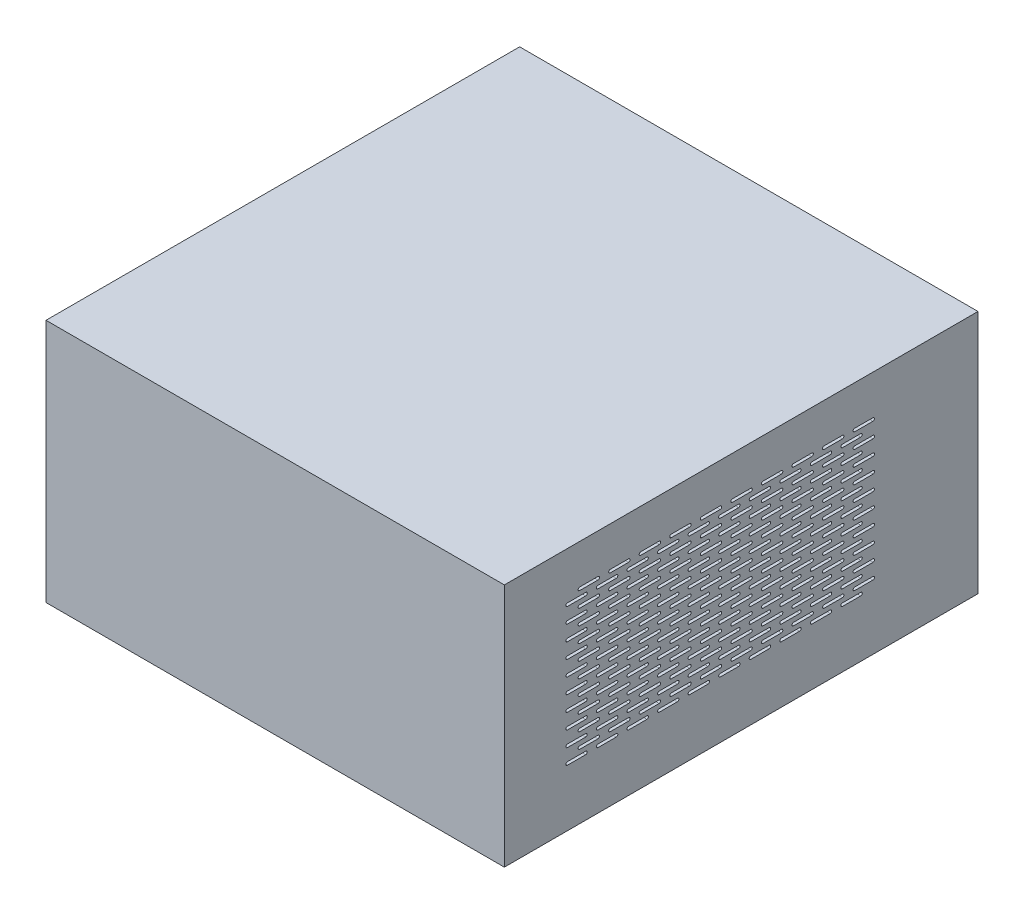
SolidWorks part; units mm, degrees
ref_plane "前视基准面" through (0, 0, 0) normal (0, 0, 1) x (1, 0, 0)
ref_plane "上视基准面" through (0, 0, 0) normal (0, 1, 0) x (1, 0, 0)
ref_plane "右视基准面" through (0, 0, 0) normal (1, 0, 0) x (0, 0, -1)
sketch "草图1" plane through (0, 0, 0) normal (0, 0, 1) x (1, 0, 0)
  line L1 (-75, 40) -> (75, 40)
  line L2 (-75, 40) -> (-75, -40)
  line L3 (-75, -40) -> (75, -40)
  line L4 (75, 40) -> (75, -40)
  line L5 (-75, 40) -> (75, -40) construction
  line L6 (-75, -40) -> (75, 40) construction
  point P0 (0, 0)
  dimension "D1" = 150
  dimension "D2" = 80
extrude "凸台-拉伸1" add sketch "草图1" along normal blind 77.5 and the other way blind 77.5 contours L1 L4 L3 L2
shell "抽壳1" thickness 2.3 removed face at (0, 0, -77.5)
sketch "草图2" plane through (75, 0, 0) normal (1, 0, 0) x (0, 0, -1)
  line L0 (-46.8721, 27.0767) -> (-52.8721, 27.0767)
  line L1 (-46.8721, 26.0767) -> (-52.8721, 26.0767)
  line L2 (-36.8721, 27.0767) -> (-42.8721, 27.0767)
  line L3 (-36.8721, 26.0767) -> (-42.8721, 26.0767)
  line L4 (-26.8721, 27.0767) -> (-32.8721, 27.0767)
  line L5 (-26.8721, 26.0767) -> (-32.8721, 26.0767)
  line L6 (-16.8721, 27.0767) -> (-22.8721, 27.0767)
  line L7 (-16.8721, 26.0767) -> (-22.8721, 26.0767)
  line L8 (-6.8721, 27.0767) -> (-12.8721, 27.0767)
  line L9 (-6.8721, 26.0767) -> (-12.8721, 26.0767)
  line L10 (3.1279, 27.0767) -> (-2.8721, 27.0767)
  line L11 (3.1279, 26.0767) -> (-2.8721, 26.0767)
  line L12 (13.1279, 27.0767) -> (7.1279, 27.0767)
  line L13 (13.1279, 26.0767) -> (7.1279, 26.0767)
  line L14 (23.1279, 27.0767) -> (17.1279, 27.0767)
  line L15 (23.1279, 26.0767) -> (17.1279, 26.0767)
  line L16 (33.1279, 27.0767) -> (27.1279, 27.0767)
  line L17 (33.1279, 26.0767) -> (27.1279, 26.0767)
  line L18 (43.1279, 27.0767) -> (37.1279, 27.0767)
  line L19 (43.1279, 26.0767) -> (37.1279, 26.0767)
  line L20 (-50.8721, 24.5767) -> (-56.8721, 24.5767)
  line L21 (-50.8721, 23.5767) -> (-56.8721, 23.5767)
  line L22 (-40.8721, 24.5767) -> (-46.8721, 24.5767)
  line L23 (-40.8721, 23.5767) -> (-46.8721, 23.5767)
  line L24 (-30.8721, 24.5767) -> (-36.8721, 24.5767)
  line L25 (-30.8721, 23.5767) -> (-36.8721, 23.5767)
  line L26 (-20.8721, 24.5767) -> (-26.8721, 24.5767)
  line L27 (-20.8721, 23.5767) -> (-26.8721, 23.5767)
  line L28 (-10.8721, 24.5767) -> (-16.8721, 24.5767)
  line L29 (-10.8721, 23.5767) -> (-16.8721, 23.5767)
  line L30 (-0.8721, 24.5767) -> (-6.8721, 24.5767)
  line L31 (-0.8721, 23.5767) -> (-6.8721, 23.5767)
  line L32 (9.1279, 24.5767) -> (3.1279, 24.5767)
  line L33 (9.1279, 23.5767) -> (3.1279, 23.5767)
  line L34 (19.1279, 24.5767) -> (13.1279, 24.5767)
  line L35 (19.1279, 23.5767) -> (13.1279, 23.5767)
  line L36 (29.1279, 24.5767) -> (23.1279, 24.5767)
  line L37 (29.1279, 23.5767) -> (23.1279, 23.5767)
  line L38 (39.1279, 24.5767) -> (33.1279, 24.5767)
  line L39 (39.1279, 23.5767) -> (33.1279, 23.5767)
  line L40 (-46.8721, 22.0767) -> (-52.8721, 22.0767)
  line L41 (-46.8721, 21.0767) -> (-52.8721, 21.0767)
  line L42 (-36.8721, 22.0767) -> (-42.8721, 22.0767)
  line L43 (-36.8721, 21.0767) -> (-42.8721, 21.0767)
  line L44 (-26.8721, 22.0767) -> (-32.8721, 22.0767)
  line L45 (-26.8721, 21.0767) -> (-32.8721, 21.0767)
  line L46 (-16.8721, 22.0767) -> (-22.8721, 22.0767)
  line L47 (-16.8721, 21.0767) -> (-22.8721, 21.0767)
  line L48 (-6.8721, 22.0767) -> (-12.8721, 22.0767)
  line L49 (-6.8721, 21.0767) -> (-12.8721, 21.0767)
  line L50 (3.1279, 22.0767) -> (-2.8721, 22.0767)
  line L51 (3.1279, 21.0767) -> (-2.8721, 21.0767)
  line L52 (13.1279, 22.0767) -> (7.1279, 22.0767)
  line L53 (13.1279, 21.0767) -> (7.1279, 21.0767)
  line L54 (23.1279, 22.0767) -> (17.1279, 22.0767)
  line L55 (23.1279, 21.0767) -> (17.1279, 21.0767)
  line L56 (33.1279, 22.0767) -> (27.1279, 22.0767)
  line L57 (33.1279, 21.0767) -> (27.1279, 21.0767)
  line L58 (43.1279, 22.0767) -> (37.1279, 22.0767)
  line L59 (43.1279, 21.0767) -> (37.1279, 21.0767)
  line L60 (-50.8721, 19.5767) -> (-56.8721, 19.5767)
  line L61 (-50.8721, 18.5767) -> (-56.8721, 18.5767)
  line L62 (-40.8721, 19.5767) -> (-46.8721, 19.5767)
  line L63 (-40.8721, 18.5767) -> (-46.8721, 18.5767)
  line L64 (-30.8721, 19.5767) -> (-36.8721, 19.5767)
  line L65 (-30.8721, 18.5767) -> (-36.8721, 18.5767)
  line L66 (-20.8721, 19.5767) -> (-26.8721, 19.5767)
  line L67 (-20.8721, 18.5767) -> (-26.8721, 18.5767)
  line L68 (-10.8721, 19.5767) -> (-16.8721, 19.5767)
  line L69 (-10.8721, 18.5767) -> (-16.8721, 18.5767)
  line L70 (-0.8721, 19.5767) -> (-6.8721, 19.5767)
  line L71 (-0.8721, 18.5767) -> (-6.8721, 18.5767)
  line L72 (9.1279, 19.5767) -> (3.1279, 19.5767)
  line L73 (9.1279, 18.5767) -> (3.1279, 18.5767)
  line L74 (19.1279, 19.5767) -> (13.1279, 19.5767)
  line L75 (19.1279, 18.5767) -> (13.1279, 18.5767)
  line L76 (29.1279, 19.5767) -> (23.1279, 19.5767)
  line L77 (29.1279, 18.5767) -> (23.1279, 18.5767)
  line L78 (39.1279, 19.5767) -> (33.1279, 19.5767)
  line L79 (39.1279, 18.5767) -> (33.1279, 18.5767)
  line L80 (-46.8721, 17.0767) -> (-52.8721, 17.0767)
  line L81 (-46.8721, 16.0767) -> (-52.8721, 16.0767)
  line L82 (-36.8721, 17.0767) -> (-42.8721, 17.0767)
  line L83 (-36.8721, 16.0767) -> (-42.8721, 16.0767)
  line L84 (-26.8721, 17.0767) -> (-32.8721, 17.0767)
  line L85 (-26.8721, 16.0767) -> (-32.8721, 16.0767)
  line L86 (-16.8721, 17.0767) -> (-22.8721, 17.0767)
  line L87 (-16.8721, 16.0767) -> (-22.8721, 16.0767)
  line L88 (-6.8721, 17.0767) -> (-12.8721, 17.0767)
  line L89 (-6.8721, 16.0767) -> (-12.8721, 16.0767)
  line L90 (3.1279, 17.0767) -> (-2.8721, 17.0767)
  line L91 (3.1279, 16.0767) -> (-2.8721, 16.0767)
  line L92 (13.1279, 17.0767) -> (7.1279, 17.0767)
  line L93 (13.1279, 16.0767) -> (7.1279, 16.0767)
  line L94 (23.1279, 17.0767) -> (17.1279, 17.0767)
  line L95 (23.1279, 16.0767) -> (17.1279, 16.0767)
  line L96 (33.1279, 17.0767) -> (27.1279, 17.0767)
  line L97 (33.1279, 16.0767) -> (27.1279, 16.0767)
  line L98 (43.1279, 17.0767) -> (37.1279, 17.0767)
  line L99 (43.1279, 16.0767) -> (37.1279, 16.0767)
  line L100 (-50.8721, 14.5767) -> (-56.8721, 14.5767)
  line L101 (-50.8721, 13.5767) -> (-56.8721, 13.5767)
  line L102 (-40.8721, 14.5767) -> (-46.8721, 14.5767)
  line L103 (-40.8721, 13.5767) -> (-46.8721, 13.5767)
  line L104 (-30.8721, 14.5767) -> (-36.8721, 14.5767)
  line L105 (-30.8721, 13.5767) -> (-36.8721, 13.5767)
  line L106 (-20.8721, 14.5767) -> (-26.8721, 14.5767)
  line L107 (-20.8721, 13.5767) -> (-26.8721, 13.5767)
  line L108 (-10.8721, 14.5767) -> (-16.8721, 14.5767)
  line L109 (-10.8721, 13.5767) -> (-16.8721, 13.5767)
  line L110 (-0.8721, 14.5767) -> (-6.8721, 14.5767)
  line L111 (-0.8721, 13.5767) -> (-6.8721, 13.5767)
  line L112 (9.1279, 14.5767) -> (3.1279, 14.5767)
  line L113 (9.1279, 13.5767) -> (3.1279, 13.5767)
  line L114 (19.1279, 14.5767) -> (13.1279, 14.5767)
  line L115 (19.1279, 13.5767) -> (13.1279, 13.5767)
  line L116 (29.1279, 14.5767) -> (23.1279, 14.5767)
  line L117 (29.1279, 13.5767) -> (23.1279, 13.5767)
  line L118 (39.1279, 14.5767) -> (33.1279, 14.5767)
  line L119 (39.1279, 13.5767) -> (33.1279, 13.5767)
  line L120 (-46.8721, 12.0767) -> (-52.8721, 12.0767)
  line L121 (-46.8721, 11.0767) -> (-52.8721, 11.0767)
  line L122 (-36.8721, 12.0767) -> (-42.8721, 12.0767)
  line L123 (-36.8721, 11.0767) -> (-42.8721, 11.0767)
  line L124 (-26.8721, 12.0767) -> (-32.8721, 12.0767)
  line L125 (-26.8721, 11.0767) -> (-32.8721, 11.0767)
  line L126 (-16.8721, 12.0767) -> (-22.8721, 12.0767)
  line L127 (-16.8721, 11.0767) -> (-22.8721, 11.0767)
  line L128 (-6.8721, 12.0767) -> (-12.8721, 12.0767)
  line L129 (-6.8721, 11.0767) -> (-12.8721, 11.0767)
  line L130 (3.1279, 12.0767) -> (-2.8721, 12.0767)
  line L131 (3.1279, 11.0767) -> (-2.8721, 11.0767)
  line L132 (13.1279, 12.0767) -> (7.1279, 12.0767)
  line L133 (13.1279, 11.0767) -> (7.1279, 11.0767)
  line L134 (23.1279, 12.0767) -> (17.1279, 12.0767)
  line L135 (23.1279, 11.0767) -> (17.1279, 11.0767)
  line L136 (33.1279, 12.0767) -> (27.1279, 12.0767)
  line L137 (33.1279, 11.0767) -> (27.1279, 11.0767)
  line L138 (43.1279, 12.0767) -> (37.1279, 12.0767)
  line L139 (43.1279, 11.0767) -> (37.1279, 11.0767)
  line L140 (-50.8721, 9.5767) -> (-56.8721, 9.5767)
  line L141 (-50.8721, 8.5767) -> (-56.8721, 8.5767)
  line L142 (-40.8721, 9.5767) -> (-46.8721, 9.5767)
  line L143 (-40.8721, 8.5767) -> (-46.8721, 8.5767)
  line L144 (-30.8721, 9.5767) -> (-36.8721, 9.5767)
  line L145 (-30.8721, 8.5767) -> (-36.8721, 8.5767)
  line L146 (-20.8721, 9.5767) -> (-26.8721, 9.5767)
  line L147 (-20.8721, 8.5767) -> (-26.8721, 8.5767)
  line L148 (-10.8721, 9.5767) -> (-16.8721, 9.5767)
  line L149 (-10.8721, 8.5767) -> (-16.8721, 8.5767)
  line L150 (-0.8721, 9.5767) -> (-6.8721, 9.5767)
  line L151 (-0.8721, 8.5767) -> (-6.8721, 8.5767)
  line L152 (9.1279, 9.5767) -> (3.1279, 9.5767)
  line L153 (9.1279, 8.5767) -> (3.1279, 8.5767)
  line L154 (19.1279, 9.5767) -> (13.1279, 9.5767)
  line L155 (19.1279, 8.5767) -> (13.1279, 8.5767)
  line L156 (29.1279, 9.5767) -> (23.1279, 9.5767)
  line L157 (29.1279, 8.5767) -> (23.1279, 8.5767)
  line L158 (39.1279, 9.5767) -> (33.1279, 9.5767)
  line L159 (39.1279, 8.5767) -> (33.1279, 8.5767)
  line L160 (-46.8721, 7.0767) -> (-52.8721, 7.0767)
  line L161 (-46.8721, 6.0767) -> (-52.8721, 6.0767)
  line L162 (-36.8721, 7.0767) -> (-42.8721, 7.0767)
  line L163 (-36.8721, 6.0767) -> (-42.8721, 6.0767)
  line L164 (-26.8721, 7.0767) -> (-32.8721, 7.0767)
  line L165 (-26.8721, 6.0767) -> (-32.8721, 6.0767)
  line L166 (-16.8721, 7.0767) -> (-22.8721, 7.0767)
  line L167 (-16.8721, 6.0767) -> (-22.8721, 6.0767)
  line L168 (-6.8721, 7.0767) -> (-12.8721, 7.0767)
  line L169 (-6.8721, 6.0767) -> (-12.8721, 6.0767)
  line L170 (3.1279, 7.0767) -> (-2.8721, 7.0767)
  line L171 (3.1279, 6.0767) -> (-2.8721, 6.0767)
  line L172 (13.1279, 7.0767) -> (7.1279, 7.0767)
  line L173 (13.1279, 6.0767) -> (7.1279, 6.0767)
  line L174 (23.1279, 7.0767) -> (17.1279, 7.0767)
  line L175 (23.1279, 6.0767) -> (17.1279, 6.0767)
  line L176 (33.1279, 7.0767) -> (27.1279, 7.0767)
  line L177 (33.1279, 6.0767) -> (27.1279, 6.0767)
  line L178 (43.1279, 7.0767) -> (37.1279, 7.0767)
  line L179 (43.1279, 6.0767) -> (37.1279, 6.0767)
  line L180 (-50.8721, 4.5767) -> (-56.8721, 4.5767)
  line L181 (-50.8721, 3.5767) -> (-56.8721, 3.5767)
  line L182 (-40.8721, 4.5767) -> (-46.8721, 4.5767)
  line L183 (-40.8721, 3.5767) -> (-46.8721, 3.5767)
  line L184 (-30.8721, 4.5767) -> (-36.8721, 4.5767)
  line L185 (-30.8721, 3.5767) -> (-36.8721, 3.5767)
  line L186 (-20.8721, 4.5767) -> (-26.8721, 4.5767)
  line L187 (-20.8721, 3.5767) -> (-26.8721, 3.5767)
  line L188 (-10.8721, 4.5767) -> (-16.8721, 4.5767)
  line L189 (-10.8721, 3.5767) -> (-16.8721, 3.5767)
  line L190 (-0.8721, 4.5767) -> (-6.8721, 4.5767)
  line L191 (-0.8721, 3.5767) -> (-6.8721, 3.5767)
  line L192 (9.1279, 4.5767) -> (3.1279, 4.5767)
  line L193 (9.1279, 3.5767) -> (3.1279, 3.5767)
  line L194 (19.1279, 4.5767) -> (13.1279, 4.5767)
  line L195 (19.1279, 3.5767) -> (13.1279, 3.5767)
  line L196 (29.1279, 4.5767) -> (23.1279, 4.5767)
  line L197 (29.1279, 3.5767) -> (23.1279, 3.5767)
  line L198 (39.1279, 4.5767) -> (33.1279, 4.5767)
  line L199 (39.1279, 3.5767) -> (33.1279, 3.5767)
  line L200 (-46.8721, 2.0767) -> (-52.8721, 2.0767)
  line L201 (-46.8721, 1.0767) -> (-52.8721, 1.0767)
  line L202 (-36.8721, 2.0767) -> (-42.8721, 2.0767)
  line L203 (-36.8721, 1.0767) -> (-42.8721, 1.0767)
  line L204 (-26.8721, 2.0767) -> (-32.8721, 2.0767)
  line L205 (-26.8721, 1.0767) -> (-32.8721, 1.0767)
  line L206 (-16.8721, 2.0767) -> (-22.8721, 2.0767)
  line L207 (-16.8721, 1.0767) -> (-22.8721, 1.0767)
  line L208 (-6.8721, 2.0767) -> (-12.8721, 2.0767)
  line L209 (-6.8721, 1.0767) -> (-12.8721, 1.0767)
  line L210 (3.1279, 2.0767) -> (-2.8721, 2.0767)
  line L211 (3.1279, 1.0767) -> (-2.8721, 1.0767)
  line L212 (13.1279, 2.0767) -> (7.1279, 2.0767)
  line L213 (13.1279, 1.0767) -> (7.1279, 1.0767)
  line L214 (23.1279, 2.0767) -> (17.1279, 2.0767)
  line L215 (23.1279, 1.0767) -> (17.1279, 1.0767)
  line L216 (33.1279, 2.0767) -> (27.1279, 2.0767)
  line L217 (33.1279, 1.0767) -> (27.1279, 1.0767)
  line L218 (43.1279, 2.0767) -> (37.1279, 2.0767)
  line L219 (43.1279, 1.0767) -> (37.1279, 1.0767)
  line L220 (-50.8721, -0.4233) -> (-56.8721, -0.4233)
  line L221 (-50.8721, -1.4233) -> (-56.8721, -1.4233)
  line L222 (-40.8721, -0.4233) -> (-46.8721, -0.4233)
  line L223 (-40.8721, -1.4233) -> (-46.8721, -1.4233)
  line L224 (-30.8721, -0.4233) -> (-36.8721, -0.4233)
  line L225 (-30.8721, -1.4233) -> (-36.8721, -1.4233)
  line L226 (-20.8721, -0.4233) -> (-26.8721, -0.4233)
  line L227 (-20.8721, -1.4233) -> (-26.8721, -1.4233)
  line L228 (-10.8721, -0.4233) -> (-16.8721, -0.4233)
  line L229 (-10.8721, -1.4233) -> (-16.8721, -1.4233)
  line L230 (-0.8721, -0.4233) -> (-6.8721, -0.4233)
  line L231 (-0.8721, -1.4233) -> (-6.8721, -1.4233)
  line L232 (9.1279, -0.4233) -> (3.1279, -0.4233)
  line L233 (9.1279, -1.4233) -> (3.1279, -1.4233)
  line L234 (19.1279, -0.4233) -> (13.1279, -0.4233)
  line L235 (19.1279, -1.4233) -> (13.1279, -1.4233)
  line L236 (29.1279, -0.4233) -> (23.1279, -0.4233)
  line L237 (29.1279, -1.4233) -> (23.1279, -1.4233)
  line L238 (39.1279, -0.4233) -> (33.1279, -0.4233)
  line L239 (39.1279, -1.4233) -> (33.1279, -1.4233)
  line L240 (-46.8721, -2.9233) -> (-52.8721, -2.9233)
  line L241 (-46.8721, -3.9233) -> (-52.8721, -3.9233)
  line L242 (-36.8721, -2.9233) -> (-42.8721, -2.9233)
  line L243 (-36.8721, -3.9233) -> (-42.8721, -3.9233)
  line L244 (-26.8721, -2.9233) -> (-32.8721, -2.9233)
  line L245 (-26.8721, -3.9233) -> (-32.8721, -3.9233)
  line L246 (-16.8721, -2.9233) -> (-22.8721, -2.9233)
  line L247 (-16.8721, -3.9233) -> (-22.8721, -3.9233)
  line L248 (-6.8721, -2.9233) -> (-12.8721, -2.9233)
  line L249 (-6.8721, -3.9233) -> (-12.8721, -3.9233)
  line L250 (3.1279, -2.9233) -> (-2.8721, -2.9233)
  line L251 (3.1279, -3.9233) -> (-2.8721, -3.9233)
  line L252 (13.1279, -2.9233) -> (7.1279, -2.9233)
  line L253 (13.1279, -3.9233) -> (7.1279, -3.9233)
  line L254 (23.1279, -2.9233) -> (17.1279, -2.9233)
  line L255 (23.1279, -3.9233) -> (17.1279, -3.9233)
  line L256 (33.1279, -2.9233) -> (27.1279, -2.9233)
  line L257 (33.1279, -3.9233) -> (27.1279, -3.9233)
  line L258 (43.1279, -2.9233) -> (37.1279, -2.9233)
  line L259 (43.1279, -3.9233) -> (37.1279, -3.9233)
  line L260 (-50.8721, -5.4233) -> (-56.8721, -5.4233)
  line L261 (-50.8721, -6.4233) -> (-56.8721, -6.4233)
  line L262 (-40.8721, -5.4233) -> (-46.8721, -5.4233)
  line L263 (-40.8721, -6.4233) -> (-46.8721, -6.4233)
  line L264 (-30.8721, -5.4233) -> (-36.8721, -5.4233)
  line L265 (-30.8721, -6.4233) -> (-36.8721, -6.4233)
  line L266 (-20.8721, -5.4233) -> (-26.8721, -5.4233)
  line L267 (-20.8721, -6.4233) -> (-26.8721, -6.4233)
  line L268 (-10.8721, -5.4233) -> (-16.8721, -5.4233)
  line L269 (-10.8721, -6.4233) -> (-16.8721, -6.4233)
  line L270 (-0.8721, -5.4233) -> (-6.8721, -5.4233)
  line L271 (-0.8721, -6.4233) -> (-6.8721, -6.4233)
  line L272 (9.1279, -5.4233) -> (3.1279, -5.4233)
  line L273 (9.1279, -6.4233) -> (3.1279, -6.4233)
  line L274 (19.1279, -5.4233) -> (13.1279, -5.4233)
  line L275 (19.1279, -6.4233) -> (13.1279, -6.4233)
  line L276 (29.1279, -5.4233) -> (23.1279, -5.4233)
  line L277 (29.1279, -6.4233) -> (23.1279, -6.4233)
  line L278 (39.1279, -5.4233) -> (33.1279, -5.4233)
  line L279 (39.1279, -6.4233) -> (33.1279, -6.4233)
  line L280 (-46.8721, -7.9233) -> (-52.8721, -7.9233)
  line L281 (-46.8721, -8.9233) -> (-52.8721, -8.9233)
  line L282 (-36.8721, -7.9233) -> (-42.8721, -7.9233)
  line L283 (-36.8721, -8.9233) -> (-42.8721, -8.9233)
  line L284 (-26.8721, -7.9233) -> (-32.8721, -7.9233)
  line L285 (-26.8721, -8.9233) -> (-32.8721, -8.9233)
  line L286 (-16.8721, -7.9233) -> (-22.8721, -7.9233)
  line L287 (-16.8721, -8.9233) -> (-22.8721, -8.9233)
  line L288 (-6.8721, -7.9233) -> (-12.8721, -7.9233)
  line L289 (-6.8721, -8.9233) -> (-12.8721, -8.9233)
  line L290 (3.1279, -7.9233) -> (-2.8721, -7.9233)
  line L291 (3.1279, -8.9233) -> (-2.8721, -8.9233)
  line L292 (13.1279, -7.9233) -> (7.1279, -7.9233)
  line L293 (13.1279, -8.9233) -> (7.1279, -8.9233)
  line L294 (23.1279, -7.9233) -> (17.1279, -7.9233)
  line L295 (23.1279, -8.9233) -> (17.1279, -8.9233)
  line L296 (33.1279, -7.9233) -> (27.1279, -7.9233)
  line L297 (33.1279, -8.9233) -> (27.1279, -8.9233)
  line L298 (43.1279, -7.9233) -> (37.1279, -7.9233)
  line L299 (43.1279, -8.9233) -> (37.1279, -8.9233)
  line L300 (-50.8721, -10.4233) -> (-56.8721, -10.4233)
  line L301 (-50.8721, -11.4233) -> (-56.8721, -11.4233)
  line L302 (-40.8721, -10.4233) -> (-46.8721, -10.4233)
  line L303 (-40.8721, -11.4233) -> (-46.8721, -11.4233)
  line L304 (-30.8721, -10.4233) -> (-36.8721, -10.4233)
  line L305 (-30.8721, -11.4233) -> (-36.8721, -11.4233)
  line L306 (-20.8721, -10.4233) -> (-26.8721, -10.4233)
  line L307 (-20.8721, -11.4233) -> (-26.8721, -11.4233)
  line L308 (-10.8721, -10.4233) -> (-16.8721, -10.4233)
  line L309 (-10.8721, -11.4233) -> (-16.8721, -11.4233)
  line L310 (-0.8721, -10.4233) -> (-6.8721, -10.4233)
  line L311 (-0.8721, -11.4233) -> (-6.8721, -11.4233)
  line L312 (9.1279, -10.4233) -> (3.1279, -10.4233)
  line L313 (9.1279, -11.4233) -> (3.1279, -11.4233)
  line L314 (19.1279, -10.4233) -> (13.1279, -10.4233)
  line L315 (19.1279, -11.4233) -> (13.1279, -11.4233)
  line L316 (29.1279, -10.4233) -> (23.1279, -10.4233)
  line L317 (29.1279, -11.4233) -> (23.1279, -11.4233)
  line L318 (39.1279, -10.4233) -> (33.1279, -10.4233)
  line L319 (39.1279, -11.4233) -> (33.1279, -11.4233)
  line L320 (-46.8721, -12.9233) -> (-52.8721, -12.9233)
  line L321 (-46.8721, -13.9233) -> (-52.8721, -13.9233)
  line L322 (-36.8721, -12.9233) -> (-42.8721, -12.9233)
  line L323 (-36.8721, -13.9233) -> (-42.8721, -13.9233)
  line L324 (-26.8721, -12.9233) -> (-32.8721, -12.9233)
  line L325 (-26.8721, -13.9233) -> (-32.8721, -13.9233)
  line L326 (-16.8721, -12.9233) -> (-22.8721, -12.9233)
  line L327 (-16.8721, -13.9233) -> (-22.8721, -13.9233)
  line L328 (-6.8721, -12.9233) -> (-12.8721, -12.9233)
  line L329 (-6.8721, -13.9233) -> (-12.8721, -13.9233)
  line L330 (3.1279, -12.9233) -> (-2.8721, -12.9233)
  line L331 (3.1279, -13.9233) -> (-2.8721, -13.9233)
  line L332 (13.1279, -12.9233) -> (7.1279, -12.9233)
  line L333 (13.1279, -13.9233) -> (7.1279, -13.9233)
  line L334 (23.1279, -12.9233) -> (17.1279, -12.9233)
  line L335 (23.1279, -13.9233) -> (17.1279, -13.9233)
  line L336 (33.1279, -12.9233) -> (27.1279, -12.9233)
  line L337 (33.1279, -13.9233) -> (27.1279, -13.9233)
  line L338 (43.1279, -12.9233) -> (37.1279, -12.9233)
  line L339 (43.1279, -13.9233) -> (37.1279, -13.9233)
  line L340 (-50.8721, -15.4233) -> (-56.8721, -15.4233)
  line L341 (-50.8721, -16.4233) -> (-56.8721, -16.4233)
  line L342 (-40.8721, -15.4233) -> (-46.8721, -15.4233)
  line L343 (-40.8721, -16.4233) -> (-46.8721, -16.4233)
  line L344 (-30.8721, -15.4233) -> (-36.8721, -15.4233)
  line L345 (-30.8721, -16.4233) -> (-36.8721, -16.4233)
  line L346 (-20.8721, -15.4233) -> (-26.8721, -15.4233)
  line L347 (-20.8721, -16.4233) -> (-26.8721, -16.4233)
  line L348 (-10.8721, -15.4233) -> (-16.8721, -15.4233)
  line L349 (-10.8721, -16.4233) -> (-16.8721, -16.4233)
  line L350 (-0.8721, -15.4233) -> (-6.8721, -15.4233)
  line L351 (-0.8721, -16.4233) -> (-6.8721, -16.4233)
  line L352 (9.1279, -15.4233) -> (3.1279, -15.4233)
  line L353 (9.1279, -16.4233) -> (3.1279, -16.4233)
  line L354 (19.1279, -15.4233) -> (13.1279, -15.4233)
  line L355 (19.1279, -16.4233) -> (13.1279, -16.4233)
  line L356 (29.1279, -15.4233) -> (23.1279, -15.4233)
  line L357 (29.1279, -16.4233) -> (23.1279, -16.4233)
  line L358 (39.1279, -15.4233) -> (33.1279, -15.4233)
  line L359 (39.1279, -16.4233) -> (33.1279, -16.4233)
  line L360 (-46.8721, -17.9233) -> (-52.8721, -17.9233)
  line L361 (-46.8721, -18.9233) -> (-52.8721, -18.9233)
  line L362 (-36.8721, -17.9233) -> (-42.8721, -17.9233)
  line L363 (-36.8721, -18.9233) -> (-42.8721, -18.9233)
  line L364 (-26.8721, -17.9233) -> (-32.8721, -17.9233)
  line L365 (-26.8721, -18.9233) -> (-32.8721, -18.9233)
  line L366 (-16.8721, -17.9233) -> (-22.8721, -17.9233)
  line L367 (-16.8721, -18.9233) -> (-22.8721, -18.9233)
  line L368 (-6.8721, -17.9233) -> (-12.8721, -17.9233)
  line L369 (-6.8721, -18.9233) -> (-12.8721, -18.9233)
  line L370 (3.1279, -17.9233) -> (-2.8721, -17.9233)
  line L371 (3.1279, -18.9233) -> (-2.8721, -18.9233)
  line L372 (13.1279, -17.9233) -> (7.1279, -17.9233)
  line L373 (13.1279, -18.9233) -> (7.1279, -18.9233)
  line L374 (23.1279, -17.9233) -> (17.1279, -17.9233)
  line L375 (23.1279, -18.9233) -> (17.1279, -18.9233)
  line L376 (33.1279, -17.9233) -> (27.1279, -17.9233)
  line L377 (33.1279, -18.9233) -> (27.1279, -18.9233)
  line L378 (43.1279, -17.9233) -> (37.1279, -17.9233)
  line L379 (43.1279, -18.9233) -> (37.1279, -18.9233)
  line L380 (-50.8721, -20.4233) -> (-56.8721, -20.4233)
  line L381 (-50.8721, -21.4233) -> (-56.8721, -21.4233)
  line L382 (-40.8721, -20.4233) -> (-46.8721, -20.4233)
  line L383 (-40.8721, -21.4233) -> (-46.8721, -21.4233)
  line L384 (-30.8721, -20.4233) -> (-36.8721, -20.4233)
  line L385 (-30.8721, -21.4233) -> (-36.8721, -21.4233)
  line L386 (-20.8721, -20.4233) -> (-26.8721, -20.4233)
  line L387 (-20.8721, -21.4233) -> (-26.8721, -21.4233)
  line L388 (-10.8721, -20.4233) -> (-16.8721, -20.4233)
  line L389 (-10.8721, -21.4233) -> (-16.8721, -21.4233)
  line L390 (-0.8721, -20.4233) -> (-6.8721, -20.4233)
  line L391 (-0.8721, -21.4233) -> (-6.8721, -21.4233)
  line L392 (9.1279, -20.4233) -> (3.1279, -20.4233)
  line L393 (9.1279, -21.4233) -> (3.1279, -21.4233)
  line L394 (19.1279, -20.4233) -> (13.1279, -20.4233)
  line L395 (19.1279, -21.4233) -> (13.1279, -21.4233)
  line L396 (29.1279, -20.4233) -> (23.1279, -20.4233)
  line L397 (29.1279, -21.4233) -> (23.1279, -21.4233)
  line L398 (39.1279, -20.4233) -> (33.1279, -20.4233)
  line L399 (39.1279, -21.4233) -> (33.1279, -21.4233)
  arc A0 (-46.8721, 26.0767) -> (-46.8721, 27.0767) centre (-46.8721, 26.5767) ccw
  arc A1 (-52.8721, 27.0767) -> (-52.8721, 26.0767) centre (-52.8721, 26.5767) ccw
  arc A2 (-36.8721, 26.0767) -> (-36.8721, 27.0767) centre (-36.8721, 26.5767) ccw
  arc A3 (-42.8721, 27.0767) -> (-42.8721, 26.0767) centre (-42.8721, 26.5767) ccw
  arc A4 (-26.8721, 26.0767) -> (-26.8721, 27.0767) centre (-26.8721, 26.5767) ccw
  arc A5 (-32.8721, 27.0767) -> (-32.8721, 26.0767) centre (-32.8721, 26.5767) ccw
  arc A6 (-16.8721, 26.0767) -> (-16.8721, 27.0767) centre (-16.8721, 26.5767) ccw
  arc A7 (-22.8721, 27.0767) -> (-22.8721, 26.0767) centre (-22.8721, 26.5767) ccw
  arc A8 (-6.8721, 26.0767) -> (-6.8721, 27.0767) centre (-6.8721, 26.5767) ccw
  arc A9 (-12.8721, 27.0767) -> (-12.8721, 26.0767) centre (-12.8721, 26.5767) ccw
  arc A10 (3.1279, 26.0767) -> (3.1279, 27.0767) centre (3.1279, 26.5767) ccw
  arc A11 (-2.8721, 27.0767) -> (-2.8721, 26.0767) centre (-2.8721, 26.5767) ccw
  arc A12 (13.1279, 26.0767) -> (13.1279, 27.0767) centre (13.1279, 26.5767) ccw
  arc A13 (7.1279, 27.0767) -> (7.1279, 26.0767) centre (7.1279, 26.5767) ccw
  arc A14 (23.1279, 26.0767) -> (23.1279, 27.0767) centre (23.1279, 26.5767) ccw
  arc A15 (17.1279, 27.0767) -> (17.1279, 26.0767) centre (17.1279, 26.5767) ccw
  arc A16 (33.1279, 26.0767) -> (33.1279, 27.0767) centre (33.1279, 26.5767) ccw
  arc A17 (27.1279, 27.0767) -> (27.1279, 26.0767) centre (27.1279, 26.5767) ccw
  arc A18 (43.1279, 26.0767) -> (43.1279, 27.0767) centre (43.1279, 26.5767) ccw
  arc A19 (37.1279, 27.0767) -> (37.1279, 26.0767) centre (37.1279, 26.5767) ccw
  arc A20 (-50.8721, 23.5767) -> (-50.8721, 24.5767) centre (-50.8721, 24.0767) ccw
  arc A21 (-56.8721, 24.5767) -> (-56.8721, 23.5767) centre (-56.8721, 24.0767) ccw
  arc A22 (-40.8721, 23.5767) -> (-40.8721, 24.5767) centre (-40.8721, 24.0767) ccw
  arc A23 (-46.8721, 24.5767) -> (-46.8721, 23.5767) centre (-46.8721, 24.0767) ccw
  arc A24 (-30.8721, 23.5767) -> (-30.8721, 24.5767) centre (-30.8721, 24.0767) ccw
  arc A25 (-36.8721, 24.5767) -> (-36.8721, 23.5767) centre (-36.8721, 24.0767) ccw
  arc A26 (-20.8721, 23.5767) -> (-20.8721, 24.5767) centre (-20.8721, 24.0767) ccw
  arc A27 (-26.8721, 24.5767) -> (-26.8721, 23.5767) centre (-26.8721, 24.0767) ccw
  arc A28 (-10.8721, 23.5767) -> (-10.8721, 24.5767) centre (-10.8721, 24.0767) ccw
  arc A29 (-16.8721, 24.5767) -> (-16.8721, 23.5767) centre (-16.8721, 24.0767) ccw
  arc A30 (-0.8721, 23.5767) -> (-0.8721, 24.5767) centre (-0.8721, 24.0767) ccw
  arc A31 (-6.8721, 24.5767) -> (-6.8721, 23.5767) centre (-6.8721, 24.0767) ccw
  arc A32 (9.1279, 23.5767) -> (9.1279, 24.5767) centre (9.1279, 24.0767) ccw
  arc A33 (3.1279, 24.5767) -> (3.1279, 23.5767) centre (3.1279, 24.0767) ccw
  arc A34 (19.1279, 23.5767) -> (19.1279, 24.5767) centre (19.1279, 24.0767) ccw
  arc A35 (13.1279, 24.5767) -> (13.1279, 23.5767) centre (13.1279, 24.0767) ccw
  arc A36 (29.1279, 23.5767) -> (29.1279, 24.5767) centre (29.1279, 24.0767) ccw
  arc A37 (23.1279, 24.5767) -> (23.1279, 23.5767) centre (23.1279, 24.0767) ccw
  arc A38 (39.1279, 23.5767) -> (39.1279, 24.5767) centre (39.1279, 24.0767) ccw
  arc A39 (33.1279, 24.5767) -> (33.1279, 23.5767) centre (33.1279, 24.0767) ccw
  arc A40 (-46.8721, 21.0767) -> (-46.8721, 22.0767) centre (-46.8721, 21.5767) ccw
  arc A41 (-52.8721, 22.0767) -> (-52.8721, 21.0767) centre (-52.8721, 21.5767) ccw
  arc A42 (-36.8721, 21.0767) -> (-36.8721, 22.0767) centre (-36.8721, 21.5767) ccw
  arc A43 (-42.8721, 22.0767) -> (-42.8721, 21.0767) centre (-42.8721, 21.5767) ccw
  arc A44 (-26.8721, 21.0767) -> (-26.8721, 22.0767) centre (-26.8721, 21.5767) ccw
  arc A45 (-32.8721, 22.0767) -> (-32.8721, 21.0767) centre (-32.8721, 21.5767) ccw
  arc A46 (-16.8721, 21.0767) -> (-16.8721, 22.0767) centre (-16.8721, 21.5767) ccw
  arc A47 (-22.8721, 22.0767) -> (-22.8721, 21.0767) centre (-22.8721, 21.5767) ccw
  arc A48 (-6.8721, 21.0767) -> (-6.8721, 22.0767) centre (-6.8721, 21.5767) ccw
  arc A49 (-12.8721, 22.0767) -> (-12.8721, 21.0767) centre (-12.8721, 21.5767) ccw
  arc A50 (3.1279, 21.0767) -> (3.1279, 22.0767) centre (3.1279, 21.5767) ccw
  arc A51 (-2.8721, 22.0767) -> (-2.8721, 21.0767) centre (-2.8721, 21.5767) ccw
  arc A52 (13.1279, 21.0767) -> (13.1279, 22.0767) centre (13.1279, 21.5767) ccw
  arc A53 (7.1279, 22.0767) -> (7.1279, 21.0767) centre (7.1279, 21.5767) ccw
  arc A54 (23.1279, 21.0767) -> (23.1279, 22.0767) centre (23.1279, 21.5767) ccw
  arc A55 (17.1279, 22.0767) -> (17.1279, 21.0767) centre (17.1279, 21.5767) ccw
  arc A56 (33.1279, 21.0767) -> (33.1279, 22.0767) centre (33.1279, 21.5767) ccw
  arc A57 (27.1279, 22.0767) -> (27.1279, 21.0767) centre (27.1279, 21.5767) ccw
  arc A58 (43.1279, 21.0767) -> (43.1279, 22.0767) centre (43.1279, 21.5767) ccw
  arc A59 (37.1279, 22.0767) -> (37.1279, 21.0767) centre (37.1279, 21.5767) ccw
  arc A60 (-50.8721, 18.5767) -> (-50.8721, 19.5767) centre (-50.8721, 19.0767) ccw
  arc A61 (-56.8721, 19.5767) -> (-56.8721, 18.5767) centre (-56.8721, 19.0767) ccw
  arc A62 (-40.8721, 18.5767) -> (-40.8721, 19.5767) centre (-40.8721, 19.0767) ccw
  arc A63 (-46.8721, 19.5767) -> (-46.8721, 18.5767) centre (-46.8721, 19.0767) ccw
  arc A64 (-30.8721, 18.5767) -> (-30.8721, 19.5767) centre (-30.8721, 19.0767) ccw
  arc A65 (-36.8721, 19.5767) -> (-36.8721, 18.5767) centre (-36.8721, 19.0767) ccw
  arc A66 (-20.8721, 18.5767) -> (-20.8721, 19.5767) centre (-20.8721, 19.0767) ccw
  arc A67 (-26.8721, 19.5767) -> (-26.8721, 18.5767) centre (-26.8721, 19.0767) ccw
  arc A68 (-10.8721, 18.5767) -> (-10.8721, 19.5767) centre (-10.8721, 19.0767) ccw
  arc A69 (-16.8721, 19.5767) -> (-16.8721, 18.5767) centre (-16.8721, 19.0767) ccw
  arc A70 (-0.8721, 18.5767) -> (-0.8721, 19.5767) centre (-0.8721, 19.0767) ccw
  arc A71 (-6.8721, 19.5767) -> (-6.8721, 18.5767) centre (-6.8721, 19.0767) ccw
  arc A72 (9.1279, 18.5767) -> (9.1279, 19.5767) centre (9.1279, 19.0767) ccw
  arc A73 (3.1279, 19.5767) -> (3.1279, 18.5767) centre (3.1279, 19.0767) ccw
  arc A74 (19.1279, 18.5767) -> (19.1279, 19.5767) centre (19.1279, 19.0767) ccw
  arc A75 (13.1279, 19.5767) -> (13.1279, 18.5767) centre (13.1279, 19.0767) ccw
  arc A76 (29.1279, 18.5767) -> (29.1279, 19.5767) centre (29.1279, 19.0767) ccw
  arc A77 (23.1279, 19.5767) -> (23.1279, 18.5767) centre (23.1279, 19.0767) ccw
  arc A78 (39.1279, 18.5767) -> (39.1279, 19.5767) centre (39.1279, 19.0767) ccw
  arc A79 (33.1279, 19.5767) -> (33.1279, 18.5767) centre (33.1279, 19.0767) ccw
  arc A80 (-46.8721, 16.0767) -> (-46.8721, 17.0767) centre (-46.8721, 16.5767) ccw
  arc A81 (-52.8721, 17.0767) -> (-52.8721, 16.0767) centre (-52.8721, 16.5767) ccw
  arc A82 (-36.8721, 16.0767) -> (-36.8721, 17.0767) centre (-36.8721, 16.5767) ccw
  arc A83 (-42.8721, 17.0767) -> (-42.8721, 16.0767) centre (-42.8721, 16.5767) ccw
  arc A84 (-26.8721, 16.0767) -> (-26.8721, 17.0767) centre (-26.8721, 16.5767) ccw
  arc A85 (-32.8721, 17.0767) -> (-32.8721, 16.0767) centre (-32.8721, 16.5767) ccw
  arc A86 (-16.8721, 16.0767) -> (-16.8721, 17.0767) centre (-16.8721, 16.5767) ccw
  arc A87 (-22.8721, 17.0767) -> (-22.8721, 16.0767) centre (-22.8721, 16.5767) ccw
  arc A88 (-6.8721, 16.0767) -> (-6.8721, 17.0767) centre (-6.8721, 16.5767) ccw
  arc A89 (-12.8721, 17.0767) -> (-12.8721, 16.0767) centre (-12.8721, 16.5767) ccw
  arc A90 (3.1279, 16.0767) -> (3.1279, 17.0767) centre (3.1279, 16.5767) ccw
  arc A91 (-2.8721, 17.0767) -> (-2.8721, 16.0767) centre (-2.8721, 16.5767) ccw
  arc A92 (13.1279, 16.0767) -> (13.1279, 17.0767) centre (13.1279, 16.5767) ccw
  arc A93 (7.1279, 17.0767) -> (7.1279, 16.0767) centre (7.1279, 16.5767) ccw
  arc A94 (23.1279, 16.0767) -> (23.1279, 17.0767) centre (23.1279, 16.5767) ccw
  arc A95 (17.1279, 17.0767) -> (17.1279, 16.0767) centre (17.1279, 16.5767) ccw
  arc A96 (33.1279, 16.0767) -> (33.1279, 17.0767) centre (33.1279, 16.5767) ccw
  arc A97 (27.1279, 17.0767) -> (27.1279, 16.0767) centre (27.1279, 16.5767) ccw
  arc A98 (43.1279, 16.0767) -> (43.1279, 17.0767) centre (43.1279, 16.5767) ccw
  arc A99 (37.1279, 17.0767) -> (37.1279, 16.0767) centre (37.1279, 16.5767) ccw
  arc A100 (-50.8721, 13.5767) -> (-50.8721, 14.5767) centre (-50.8721, 14.0767) ccw
  arc A101 (-56.8721, 14.5767) -> (-56.8721, 13.5767) centre (-56.8721, 14.0767) ccw
  arc A102 (-40.8721, 13.5767) -> (-40.8721, 14.5767) centre (-40.8721, 14.0767) ccw
  arc A103 (-46.8721, 14.5767) -> (-46.8721, 13.5767) centre (-46.8721, 14.0767) ccw
  arc A104 (-30.8721, 13.5767) -> (-30.8721, 14.5767) centre (-30.8721, 14.0767) ccw
  arc A105 (-36.8721, 14.5767) -> (-36.8721, 13.5767) centre (-36.8721, 14.0767) ccw
  arc A106 (-20.8721, 13.5767) -> (-20.8721, 14.5767) centre (-20.8721, 14.0767) ccw
  arc A107 (-26.8721, 14.5767) -> (-26.8721, 13.5767) centre (-26.8721, 14.0767) ccw
  arc A108 (-10.8721, 13.5767) -> (-10.8721, 14.5767) centre (-10.8721, 14.0767) ccw
  arc A109 (-16.8721, 14.5767) -> (-16.8721, 13.5767) centre (-16.8721, 14.0767) ccw
  arc A110 (-0.8721, 13.5767) -> (-0.8721, 14.5767) centre (-0.8721, 14.0767) ccw
  arc A111 (-6.8721, 14.5767) -> (-6.8721, 13.5767) centre (-6.8721, 14.0767) ccw
  arc A112 (9.1279, 13.5767) -> (9.1279, 14.5767) centre (9.1279, 14.0767) ccw
  arc A113 (3.1279, 14.5767) -> (3.1279, 13.5767) centre (3.1279, 14.0767) ccw
  arc A114 (19.1279, 13.5767) -> (19.1279, 14.5767) centre (19.1279, 14.0767) ccw
  arc A115 (13.1279, 14.5767) -> (13.1279, 13.5767) centre (13.1279, 14.0767) ccw
  arc A116 (29.1279, 13.5767) -> (29.1279, 14.5767) centre (29.1279, 14.0767) ccw
  arc A117 (23.1279, 14.5767) -> (23.1279, 13.5767) centre (23.1279, 14.0767) ccw
  arc A118 (39.1279, 13.5767) -> (39.1279, 14.5767) centre (39.1279, 14.0767) ccw
  arc A119 (33.1279, 14.5767) -> (33.1279, 13.5767) centre (33.1279, 14.0767) ccw
  arc A120 (-46.8721, 11.0767) -> (-46.8721, 12.0767) centre (-46.8721, 11.5767) ccw
  arc A121 (-52.8721, 12.0767) -> (-52.8721, 11.0767) centre (-52.8721, 11.5767) ccw
  arc A122 (-36.8721, 11.0767) -> (-36.8721, 12.0767) centre (-36.8721, 11.5767) ccw
  arc A123 (-42.8721, 12.0767) -> (-42.8721, 11.0767) centre (-42.8721, 11.5767) ccw
  arc A124 (-26.8721, 11.0767) -> (-26.8721, 12.0767) centre (-26.8721, 11.5767) ccw
  arc A125 (-32.8721, 12.0767) -> (-32.8721, 11.0767) centre (-32.8721, 11.5767) ccw
  arc A126 (-16.8721, 11.0767) -> (-16.8721, 12.0767) centre (-16.8721, 11.5767) ccw
  arc A127 (-22.8721, 12.0767) -> (-22.8721, 11.0767) centre (-22.8721, 11.5767) ccw
  arc A128 (-6.8721, 11.0767) -> (-6.8721, 12.0767) centre (-6.8721, 11.5767) ccw
  arc A129 (-12.8721, 12.0767) -> (-12.8721, 11.0767) centre (-12.8721, 11.5767) ccw
  arc A130 (3.1279, 11.0767) -> (3.1279, 12.0767) centre (3.1279, 11.5767) ccw
  arc A131 (-2.8721, 12.0767) -> (-2.8721, 11.0767) centre (-2.8721, 11.5767) ccw
  arc A132 (13.1279, 11.0767) -> (13.1279, 12.0767) centre (13.1279, 11.5767) ccw
  arc A133 (7.1279, 12.0767) -> (7.1279, 11.0767) centre (7.1279, 11.5767) ccw
  arc A134 (23.1279, 11.0767) -> (23.1279, 12.0767) centre (23.1279, 11.5767) ccw
  arc A135 (17.1279, 12.0767) -> (17.1279, 11.0767) centre (17.1279, 11.5767) ccw
  arc A136 (33.1279, 11.0767) -> (33.1279, 12.0767) centre (33.1279, 11.5767) ccw
  arc A137 (27.1279, 12.0767) -> (27.1279, 11.0767) centre (27.1279, 11.5767) ccw
  arc A138 (43.1279, 11.0767) -> (43.1279, 12.0767) centre (43.1279, 11.5767) ccw
  arc A139 (37.1279, 12.0767) -> (37.1279, 11.0767) centre (37.1279, 11.5767) ccw
  arc A140 (-50.8721, 8.5767) -> (-50.8721, 9.5767) centre (-50.8721, 9.0767) ccw
  arc A141 (-56.8721, 9.5767) -> (-56.8721, 8.5767) centre (-56.8721, 9.0767) ccw
  arc A142 (-40.8721, 8.5767) -> (-40.8721, 9.5767) centre (-40.8721, 9.0767) ccw
  arc A143 (-46.8721, 9.5767) -> (-46.8721, 8.5767) centre (-46.8721, 9.0767) ccw
  arc A144 (-30.8721, 8.5767) -> (-30.8721, 9.5767) centre (-30.8721, 9.0767) ccw
  arc A145 (-36.8721, 9.5767) -> (-36.8721, 8.5767) centre (-36.8721, 9.0767) ccw
  arc A146 (-20.8721, 8.5767) -> (-20.8721, 9.5767) centre (-20.8721, 9.0767) ccw
  arc A147 (-26.8721, 9.5767) -> (-26.8721, 8.5767) centre (-26.8721, 9.0767) ccw
  arc A148 (-10.8721, 8.5767) -> (-10.8721, 9.5767) centre (-10.8721, 9.0767) ccw
  arc A149 (-16.8721, 9.5767) -> (-16.8721, 8.5767) centre (-16.8721, 9.0767) ccw
  arc A150 (-0.8721, 8.5767) -> (-0.8721, 9.5767) centre (-0.8721, 9.0767) ccw
  arc A151 (-6.8721, 9.5767) -> (-6.8721, 8.5767) centre (-6.8721, 9.0767) ccw
  arc A152 (9.1279, 8.5767) -> (9.1279, 9.5767) centre (9.1279, 9.0767) ccw
  arc A153 (3.1279, 9.5767) -> (3.1279, 8.5767) centre (3.1279, 9.0767) ccw
  arc A154 (19.1279, 8.5767) -> (19.1279, 9.5767) centre (19.1279, 9.0767) ccw
  arc A155 (13.1279, 9.5767) -> (13.1279, 8.5767) centre (13.1279, 9.0767) ccw
  arc A156 (29.1279, 8.5767) -> (29.1279, 9.5767) centre (29.1279, 9.0767) ccw
  arc A157 (23.1279, 9.5767) -> (23.1279, 8.5767) centre (23.1279, 9.0767) ccw
  arc A158 (39.1279, 8.5767) -> (39.1279, 9.5767) centre (39.1279, 9.0767) ccw
  arc A159 (33.1279, 9.5767) -> (33.1279, 8.5767) centre (33.1279, 9.0767) ccw
  arc A160 (-46.8721, 6.0767) -> (-46.8721, 7.0767) centre (-46.8721, 6.5767) ccw
  arc A161 (-52.8721, 7.0767) -> (-52.8721, 6.0767) centre (-52.8721, 6.5767) ccw
  arc A162 (-36.8721, 6.0767) -> (-36.8721, 7.0767) centre (-36.8721, 6.5767) ccw
  arc A163 (-42.8721, 7.0767) -> (-42.8721, 6.0767) centre (-42.8721, 6.5767) ccw
  arc A164 (-26.8721, 6.0767) -> (-26.8721, 7.0767) centre (-26.8721, 6.5767) ccw
  arc A165 (-32.8721, 7.0767) -> (-32.8721, 6.0767) centre (-32.8721, 6.5767) ccw
  arc A166 (-16.8721, 6.0767) -> (-16.8721, 7.0767) centre (-16.8721, 6.5767) ccw
  arc A167 (-22.8721, 7.0767) -> (-22.8721, 6.0767) centre (-22.8721, 6.5767) ccw
  arc A168 (-6.8721, 6.0767) -> (-6.8721, 7.0767) centre (-6.8721, 6.5767) ccw
  arc A169 (-12.8721, 7.0767) -> (-12.8721, 6.0767) centre (-12.8721, 6.5767) ccw
  arc A170 (3.1279, 6.0767) -> (3.1279, 7.0767) centre (3.1279, 6.5767) ccw
  arc A171 (-2.8721, 7.0767) -> (-2.8721, 6.0767) centre (-2.8721, 6.5767) ccw
  arc A172 (13.1279, 6.0767) -> (13.1279, 7.0767) centre (13.1279, 6.5767) ccw
  arc A173 (7.1279, 7.0767) -> (7.1279, 6.0767) centre (7.1279, 6.5767) ccw
  arc A174 (23.1279, 6.0767) -> (23.1279, 7.0767) centre (23.1279, 6.5767) ccw
  arc A175 (17.1279, 7.0767) -> (17.1279, 6.0767) centre (17.1279, 6.5767) ccw
  arc A176 (33.1279, 6.0767) -> (33.1279, 7.0767) centre (33.1279, 6.5767) ccw
  arc A177 (27.1279, 7.0767) -> (27.1279, 6.0767) centre (27.1279, 6.5767) ccw
  arc A178 (43.1279, 6.0767) -> (43.1279, 7.0767) centre (43.1279, 6.5767) ccw
  arc A179 (37.1279, 7.0767) -> (37.1279, 6.0767) centre (37.1279, 6.5767) ccw
  arc A180 (-50.8721, 3.5767) -> (-50.8721, 4.5767) centre (-50.8721, 4.0767) ccw
  arc A181 (-56.8721, 4.5767) -> (-56.8721, 3.5767) centre (-56.8721, 4.0767) ccw
  arc A182 (-40.8721, 3.5767) -> (-40.8721, 4.5767) centre (-40.8721, 4.0767) ccw
  arc A183 (-46.8721, 4.5767) -> (-46.8721, 3.5767) centre (-46.8721, 4.0767) ccw
  arc A184 (-30.8721, 3.5767) -> (-30.8721, 4.5767) centre (-30.8721, 4.0767) ccw
  arc A185 (-36.8721, 4.5767) -> (-36.8721, 3.5767) centre (-36.8721, 4.0767) ccw
  arc A186 (-20.8721, 3.5767) -> (-20.8721, 4.5767) centre (-20.8721, 4.0767) ccw
  arc A187 (-26.8721, 4.5767) -> (-26.8721, 3.5767) centre (-26.8721, 4.0767) ccw
  arc A188 (-10.8721, 3.5767) -> (-10.8721, 4.5767) centre (-10.8721, 4.0767) ccw
  arc A189 (-16.8721, 4.5767) -> (-16.8721, 3.5767) centre (-16.8721, 4.0767) ccw
  arc A190 (-0.8721, 3.5767) -> (-0.8721, 4.5767) centre (-0.8721, 4.0767) ccw
  arc A191 (-6.8721, 4.5767) -> (-6.8721, 3.5767) centre (-6.8721, 4.0767) ccw
  arc A192 (9.1279, 3.5767) -> (9.1279, 4.5767) centre (9.1279, 4.0767) ccw
  arc A193 (3.1279, 4.5767) -> (3.1279, 3.5767) centre (3.1279, 4.0767) ccw
  arc A194 (19.1279, 3.5767) -> (19.1279, 4.5767) centre (19.1279, 4.0767) ccw
  arc A195 (13.1279, 4.5767) -> (13.1279, 3.5767) centre (13.1279, 4.0767) ccw
  arc A196 (29.1279, 3.5767) -> (29.1279, 4.5767) centre (29.1279, 4.0767) ccw
  arc A197 (23.1279, 4.5767) -> (23.1279, 3.5767) centre (23.1279, 4.0767) ccw
  arc A198 (39.1279, 3.5767) -> (39.1279, 4.5767) centre (39.1279, 4.0767) ccw
  arc A199 (33.1279, 4.5767) -> (33.1279, 3.5767) centre (33.1279, 4.0767) ccw
  arc A200 (-46.8721, 1.0767) -> (-46.8721, 2.0767) centre (-46.8721, 1.5767) ccw
  arc A201 (-52.8721, 2.0767) -> (-52.8721, 1.0767) centre (-52.8721, 1.5767) ccw
  arc A202 (-36.8721, 1.0767) -> (-36.8721, 2.0767) centre (-36.8721, 1.5767) ccw
  arc A203 (-42.8721, 2.0767) -> (-42.8721, 1.0767) centre (-42.8721, 1.5767) ccw
  arc A204 (-26.8721, 1.0767) -> (-26.8721, 2.0767) centre (-26.8721, 1.5767) ccw
  arc A205 (-32.8721, 2.0767) -> (-32.8721, 1.0767) centre (-32.8721, 1.5767) ccw
  arc A206 (-16.8721, 1.0767) -> (-16.8721, 2.0767) centre (-16.8721, 1.5767) ccw
  arc A207 (-22.8721, 2.0767) -> (-22.8721, 1.0767) centre (-22.8721, 1.5767) ccw
  arc A208 (-6.8721, 1.0767) -> (-6.8721, 2.0767) centre (-6.8721, 1.5767) ccw
  arc A209 (-12.8721, 2.0767) -> (-12.8721, 1.0767) centre (-12.8721, 1.5767) ccw
  arc A210 (3.1279, 1.0767) -> (3.1279, 2.0767) centre (3.1279, 1.5767) ccw
  arc A211 (-2.8721, 2.0767) -> (-2.8721, 1.0767) centre (-2.8721, 1.5767) ccw
  arc A212 (13.1279, 1.0767) -> (13.1279, 2.0767) centre (13.1279, 1.5767) ccw
  arc A213 (7.1279, 2.0767) -> (7.1279, 1.0767) centre (7.1279, 1.5767) ccw
  arc A214 (23.1279, 1.0767) -> (23.1279, 2.0767) centre (23.1279, 1.5767) ccw
  arc A215 (17.1279, 2.0767) -> (17.1279, 1.0767) centre (17.1279, 1.5767) ccw
  arc A216 (33.1279, 1.0767) -> (33.1279, 2.0767) centre (33.1279, 1.5767) ccw
  arc A217 (27.1279, 2.0767) -> (27.1279, 1.0767) centre (27.1279, 1.5767) ccw
  arc A218 (43.1279, 1.0767) -> (43.1279, 2.0767) centre (43.1279, 1.5767) ccw
  arc A219 (37.1279, 2.0767) -> (37.1279, 1.0767) centre (37.1279, 1.5767) ccw
  arc A220 (-50.8721, -1.4233) -> (-50.8721, -0.4233) centre (-50.8721, -0.9233) ccw
  arc A221 (-56.8721, -0.4233) -> (-56.8721, -1.4233) centre (-56.8721, -0.9233) ccw
  arc A222 (-40.8721, -1.4233) -> (-40.8721, -0.4233) centre (-40.8721, -0.9233) ccw
  arc A223 (-46.8721, -0.4233) -> (-46.8721, -1.4233) centre (-46.8721, -0.9233) ccw
  arc A224 (-30.8721, -1.4233) -> (-30.8721, -0.4233) centre (-30.8721, -0.9233) ccw
  arc A225 (-36.8721, -0.4233) -> (-36.8721, -1.4233) centre (-36.8721, -0.9233) ccw
  arc A226 (-20.8721, -1.4233) -> (-20.8721, -0.4233) centre (-20.8721, -0.9233) ccw
  arc A227 (-26.8721, -0.4233) -> (-26.8721, -1.4233) centre (-26.8721, -0.9233) ccw
  arc A228 (-10.8721, -1.4233) -> (-10.8721, -0.4233) centre (-10.8721, -0.9233) ccw
  arc A229 (-16.8721, -0.4233) -> (-16.8721, -1.4233) centre (-16.8721, -0.9233) ccw
  arc A230 (-0.8721, -1.4233) -> (-0.8721, -0.4233) centre (-0.8721, -0.9233) ccw
  arc A231 (-6.8721, -0.4233) -> (-6.8721, -1.4233) centre (-6.8721, -0.9233) ccw
  arc A232 (9.1279, -1.4233) -> (9.1279, -0.4233) centre (9.1279, -0.9233) ccw
  arc A233 (3.1279, -0.4233) -> (3.1279, -1.4233) centre (3.1279, -0.9233) ccw
  arc A234 (19.1279, -1.4233) -> (19.1279, -0.4233) centre (19.1279, -0.9233) ccw
  arc A235 (13.1279, -0.4233) -> (13.1279, -1.4233) centre (13.1279, -0.9233) ccw
  arc A236 (29.1279, -1.4233) -> (29.1279, -0.4233) centre (29.1279, -0.9233) ccw
  arc A237 (23.1279, -0.4233) -> (23.1279, -1.4233) centre (23.1279, -0.9233) ccw
  arc A238 (39.1279, -1.4233) -> (39.1279, -0.4233) centre (39.1279, -0.9233) ccw
  arc A239 (33.1279, -0.4233) -> (33.1279, -1.4233) centre (33.1279, -0.9233) ccw
  arc A240 (-46.8721, -3.9233) -> (-46.8721, -2.9233) centre (-46.8721, -3.4233) ccw
  arc A241 (-52.8721, -2.9233) -> (-52.8721, -3.9233) centre (-52.8721, -3.4233) ccw
  arc A242 (-36.8721, -3.9233) -> (-36.8721, -2.9233) centre (-36.8721, -3.4233) ccw
  arc A243 (-42.8721, -2.9233) -> (-42.8721, -3.9233) centre (-42.8721, -3.4233) ccw
  arc A244 (-26.8721, -3.9233) -> (-26.8721, -2.9233) centre (-26.8721, -3.4233) ccw
  arc A245 (-32.8721, -2.9233) -> (-32.8721, -3.9233) centre (-32.8721, -3.4233) ccw
  arc A246 (-16.8721, -3.9233) -> (-16.8721, -2.9233) centre (-16.8721, -3.4233) ccw
  arc A247 (-22.8721, -2.9233) -> (-22.8721, -3.9233) centre (-22.8721, -3.4233) ccw
  arc A248 (-6.8721, -3.9233) -> (-6.8721, -2.9233) centre (-6.8721, -3.4233) ccw
  arc A249 (-12.8721, -2.9233) -> (-12.8721, -3.9233) centre (-12.8721, -3.4233) ccw
  arc A250 (3.1279, -3.9233) -> (3.1279, -2.9233) centre (3.1279, -3.4233) ccw
  arc A251 (-2.8721, -2.9233) -> (-2.8721, -3.9233) centre (-2.8721, -3.4233) ccw
  arc A252 (13.1279, -3.9233) -> (13.1279, -2.9233) centre (13.1279, -3.4233) ccw
  arc A253 (7.1279, -2.9233) -> (7.1279, -3.9233) centre (7.1279, -3.4233) ccw
  arc A254 (23.1279, -3.9233) -> (23.1279, -2.9233) centre (23.1279, -3.4233) ccw
  arc A255 (17.1279, -2.9233) -> (17.1279, -3.9233) centre (17.1279, -3.4233) ccw
  arc A256 (33.1279, -3.9233) -> (33.1279, -2.9233) centre (33.1279, -3.4233) ccw
  arc A257 (27.1279, -2.9233) -> (27.1279, -3.9233) centre (27.1279, -3.4233) ccw
  arc A258 (43.1279, -3.9233) -> (43.1279, -2.9233) centre (43.1279, -3.4233) ccw
  arc A259 (37.1279, -2.9233) -> (37.1279, -3.9233) centre (37.1279, -3.4233) ccw
  arc A260 (-50.8721, -6.4233) -> (-50.8721, -5.4233) centre (-50.8721, -5.9233) ccw
  arc A261 (-56.8721, -5.4233) -> (-56.8721, -6.4233) centre (-56.8721, -5.9233) ccw
  arc A262 (-40.8721, -6.4233) -> (-40.8721, -5.4233) centre (-40.8721, -5.9233) ccw
  arc A263 (-46.8721, -5.4233) -> (-46.8721, -6.4233) centre (-46.8721, -5.9233) ccw
  arc A264 (-30.8721, -6.4233) -> (-30.8721, -5.4233) centre (-30.8721, -5.9233) ccw
  arc A265 (-36.8721, -5.4233) -> (-36.8721, -6.4233) centre (-36.8721, -5.9233) ccw
  arc A266 (-20.8721, -6.4233) -> (-20.8721, -5.4233) centre (-20.8721, -5.9233) ccw
  arc A267 (-26.8721, -5.4233) -> (-26.8721, -6.4233) centre (-26.8721, -5.9233) ccw
  arc A268 (-10.8721, -6.4233) -> (-10.8721, -5.4233) centre (-10.8721, -5.9233) ccw
  arc A269 (-16.8721, -5.4233) -> (-16.8721, -6.4233) centre (-16.8721, -5.9233) ccw
  arc A270 (-0.8721, -6.4233) -> (-0.8721, -5.4233) centre (-0.8721, -5.9233) ccw
  arc A271 (-6.8721, -5.4233) -> (-6.8721, -6.4233) centre (-6.8721, -5.9233) ccw
  arc A272 (9.1279, -6.4233) -> (9.1279, -5.4233) centre (9.1279, -5.9233) ccw
  arc A273 (3.1279, -5.4233) -> (3.1279, -6.4233) centre (3.1279, -5.9233) ccw
  arc A274 (19.1279, -6.4233) -> (19.1279, -5.4233) centre (19.1279, -5.9233) ccw
  arc A275 (13.1279, -5.4233) -> (13.1279, -6.4233) centre (13.1279, -5.9233) ccw
  arc A276 (29.1279, -6.4233) -> (29.1279, -5.4233) centre (29.1279, -5.9233) ccw
  arc A277 (23.1279, -5.4233) -> (23.1279, -6.4233) centre (23.1279, -5.9233) ccw
  arc A278 (39.1279, -6.4233) -> (39.1279, -5.4233) centre (39.1279, -5.9233) ccw
  arc A279 (33.1279, -5.4233) -> (33.1279, -6.4233) centre (33.1279, -5.9233) ccw
  arc A280 (-46.8721, -8.9233) -> (-46.8721, -7.9233) centre (-46.8721, -8.4233) ccw
  arc A281 (-52.8721, -7.9233) -> (-52.8721, -8.9233) centre (-52.8721, -8.4233) ccw
  arc A282 (-36.8721, -8.9233) -> (-36.8721, -7.9233) centre (-36.8721, -8.4233) ccw
  arc A283 (-42.8721, -7.9233) -> (-42.8721, -8.9233) centre (-42.8721, -8.4233) ccw
  arc A284 (-26.8721, -8.9233) -> (-26.8721, -7.9233) centre (-26.8721, -8.4233) ccw
  arc A285 (-32.8721, -7.9233) -> (-32.8721, -8.9233) centre (-32.8721, -8.4233) ccw
  arc A286 (-16.8721, -8.9233) -> (-16.8721, -7.9233) centre (-16.8721, -8.4233) ccw
  arc A287 (-22.8721, -7.9233) -> (-22.8721, -8.9233) centre (-22.8721, -8.4233) ccw
  arc A288 (-6.8721, -8.9233) -> (-6.8721, -7.9233) centre (-6.8721, -8.4233) ccw
  arc A289 (-12.8721, -7.9233) -> (-12.8721, -8.9233) centre (-12.8721, -8.4233) ccw
  arc A290 (3.1279, -8.9233) -> (3.1279, -7.9233) centre (3.1279, -8.4233) ccw
  arc A291 (-2.8721, -7.9233) -> (-2.8721, -8.9233) centre (-2.8721, -8.4233) ccw
  arc A292 (13.1279, -8.9233) -> (13.1279, -7.9233) centre (13.1279, -8.4233) ccw
  arc A293 (7.1279, -7.9233) -> (7.1279, -8.9233) centre (7.1279, -8.4233) ccw
  arc A294 (23.1279, -8.9233) -> (23.1279, -7.9233) centre (23.1279, -8.4233) ccw
  arc A295 (17.1279, -7.9233) -> (17.1279, -8.9233) centre (17.1279, -8.4233) ccw
  arc A296 (33.1279, -8.9233) -> (33.1279, -7.9233) centre (33.1279, -8.4233) ccw
  arc A297 (27.1279, -7.9233) -> (27.1279, -8.9233) centre (27.1279, -8.4233) ccw
  arc A298 (43.1279, -8.9233) -> (43.1279, -7.9233) centre (43.1279, -8.4233) ccw
  arc A299 (37.1279, -7.9233) -> (37.1279, -8.9233) centre (37.1279, -8.4233) ccw
  arc A300 (-50.8721, -11.4233) -> (-50.8721, -10.4233) centre (-50.8721, -10.9233) ccw
  arc A301 (-56.8721, -10.4233) -> (-56.8721, -11.4233) centre (-56.8721, -10.9233) ccw
  arc A302 (-40.8721, -11.4233) -> (-40.8721, -10.4233) centre (-40.8721, -10.9233) ccw
  arc A303 (-46.8721, -10.4233) -> (-46.8721, -11.4233) centre (-46.8721, -10.9233) ccw
  arc A304 (-30.8721, -11.4233) -> (-30.8721, -10.4233) centre (-30.8721, -10.9233) ccw
  arc A305 (-36.8721, -10.4233) -> (-36.8721, -11.4233) centre (-36.8721, -10.9233) ccw
  arc A306 (-20.8721, -11.4233) -> (-20.8721, -10.4233) centre (-20.8721, -10.9233) ccw
  arc A307 (-26.8721, -10.4233) -> (-26.8721, -11.4233) centre (-26.8721, -10.9233) ccw
  arc A308 (-10.8721, -11.4233) -> (-10.8721, -10.4233) centre (-10.8721, -10.9233) ccw
  arc A309 (-16.8721, -10.4233) -> (-16.8721, -11.4233) centre (-16.8721, -10.9233) ccw
  arc A310 (-0.8721, -11.4233) -> (-0.8721, -10.4233) centre (-0.8721, -10.9233) ccw
  arc A311 (-6.8721, -10.4233) -> (-6.8721, -11.4233) centre (-6.8721, -10.9233) ccw
  arc A312 (9.1279, -11.4233) -> (9.1279, -10.4233) centre (9.1279, -10.9233) ccw
  arc A313 (3.1279, -10.4233) -> (3.1279, -11.4233) centre (3.1279, -10.9233) ccw
  arc A314 (19.1279, -11.4233) -> (19.1279, -10.4233) centre (19.1279, -10.9233) ccw
  arc A315 (13.1279, -10.4233) -> (13.1279, -11.4233) centre (13.1279, -10.9233) ccw
  arc A316 (29.1279, -11.4233) -> (29.1279, -10.4233) centre (29.1279, -10.9233) ccw
  arc A317 (23.1279, -10.4233) -> (23.1279, -11.4233) centre (23.1279, -10.9233) ccw
  arc A318 (39.1279, -11.4233) -> (39.1279, -10.4233) centre (39.1279, -10.9233) ccw
  arc A319 (33.1279, -10.4233) -> (33.1279, -11.4233) centre (33.1279, -10.9233) ccw
  arc A320 (-46.8721, -13.9233) -> (-46.8721, -12.9233) centre (-46.8721, -13.4233) ccw
  arc A321 (-52.8721, -12.9233) -> (-52.8721, -13.9233) centre (-52.8721, -13.4233) ccw
  arc A322 (-36.8721, -13.9233) -> (-36.8721, -12.9233) centre (-36.8721, -13.4233) ccw
  arc A323 (-42.8721, -12.9233) -> (-42.8721, -13.9233) centre (-42.8721, -13.4233) ccw
  arc A324 (-26.8721, -13.9233) -> (-26.8721, -12.9233) centre (-26.8721, -13.4233) ccw
  arc A325 (-32.8721, -12.9233) -> (-32.8721, -13.9233) centre (-32.8721, -13.4233) ccw
  arc A326 (-16.8721, -13.9233) -> (-16.8721, -12.9233) centre (-16.8721, -13.4233) ccw
  arc A327 (-22.8721, -12.9233) -> (-22.8721, -13.9233) centre (-22.8721, -13.4233) ccw
  arc A328 (-6.8721, -13.9233) -> (-6.8721, -12.9233) centre (-6.8721, -13.4233) ccw
  arc A329 (-12.8721, -12.9233) -> (-12.8721, -13.9233) centre (-12.8721, -13.4233) ccw
  arc A330 (3.1279, -13.9233) -> (3.1279, -12.9233) centre (3.1279, -13.4233) ccw
  arc A331 (-2.8721, -12.9233) -> (-2.8721, -13.9233) centre (-2.8721, -13.4233) ccw
  arc A332 (13.1279, -13.9233) -> (13.1279, -12.9233) centre (13.1279, -13.4233) ccw
  arc A333 (7.1279, -12.9233) -> (7.1279, -13.9233) centre (7.1279, -13.4233) ccw
  arc A334 (23.1279, -13.9233) -> (23.1279, -12.9233) centre (23.1279, -13.4233) ccw
  arc A335 (17.1279, -12.9233) -> (17.1279, -13.9233) centre (17.1279, -13.4233) ccw
  arc A336 (33.1279, -13.9233) -> (33.1279, -12.9233) centre (33.1279, -13.4233) ccw
  arc A337 (27.1279, -12.9233) -> (27.1279, -13.9233) centre (27.1279, -13.4233) ccw
  arc A338 (43.1279, -13.9233) -> (43.1279, -12.9233) centre (43.1279, -13.4233) ccw
  arc A339 (37.1279, -12.9233) -> (37.1279, -13.9233) centre (37.1279, -13.4233) ccw
  arc A340 (-50.8721, -16.4233) -> (-50.8721, -15.4233) centre (-50.8721, -15.9233) ccw
  arc A341 (-56.8721, -15.4233) -> (-56.8721, -16.4233) centre (-56.8721, -15.9233) ccw
  arc A342 (-40.8721, -16.4233) -> (-40.8721, -15.4233) centre (-40.8721, -15.9233) ccw
  arc A343 (-46.8721, -15.4233) -> (-46.8721, -16.4233) centre (-46.8721, -15.9233) ccw
  arc A344 (-30.8721, -16.4233) -> (-30.8721, -15.4233) centre (-30.8721, -15.9233) ccw
  arc A345 (-36.8721, -15.4233) -> (-36.8721, -16.4233) centre (-36.8721, -15.9233) ccw
  arc A346 (-20.8721, -16.4233) -> (-20.8721, -15.4233) centre (-20.8721, -15.9233) ccw
  arc A347 (-26.8721, -15.4233) -> (-26.8721, -16.4233) centre (-26.8721, -15.9233) ccw
  arc A348 (-10.8721, -16.4233) -> (-10.8721, -15.4233) centre (-10.8721, -15.9233) ccw
  arc A349 (-16.8721, -15.4233) -> (-16.8721, -16.4233) centre (-16.8721, -15.9233) ccw
  arc A350 (-0.8721, -16.4233) -> (-0.8721, -15.4233) centre (-0.8721, -15.9233) ccw
  arc A351 (-6.8721, -15.4233) -> (-6.8721, -16.4233) centre (-6.8721, -15.9233) ccw
  arc A352 (9.1279, -16.4233) -> (9.1279, -15.4233) centre (9.1279, -15.9233) ccw
  arc A353 (3.1279, -15.4233) -> (3.1279, -16.4233) centre (3.1279, -15.9233) ccw
  arc A354 (19.1279, -16.4233) -> (19.1279, -15.4233) centre (19.1279, -15.9233) ccw
  arc A355 (13.1279, -15.4233) -> (13.1279, -16.4233) centre (13.1279, -15.9233) ccw
  arc A356 (29.1279, -16.4233) -> (29.1279, -15.4233) centre (29.1279, -15.9233) ccw
  arc A357 (23.1279, -15.4233) -> (23.1279, -16.4233) centre (23.1279, -15.9233) ccw
  arc A358 (39.1279, -16.4233) -> (39.1279, -15.4233) centre (39.1279, -15.9233) ccw
  arc A359 (33.1279, -15.4233) -> (33.1279, -16.4233) centre (33.1279, -15.9233) ccw
  arc A360 (-46.8721, -18.9233) -> (-46.8721, -17.9233) centre (-46.8721, -18.4233) ccw
  arc A361 (-52.8721, -17.9233) -> (-52.8721, -18.9233) centre (-52.8721, -18.4233) ccw
  arc A362 (-36.8721, -18.9233) -> (-36.8721, -17.9233) centre (-36.8721, -18.4233) ccw
  arc A363 (-42.8721, -17.9233) -> (-42.8721, -18.9233) centre (-42.8721, -18.4233) ccw
  arc A364 (-26.8721, -18.9233) -> (-26.8721, -17.9233) centre (-26.8721, -18.4233) ccw
  arc A365 (-32.8721, -17.9233) -> (-32.8721, -18.9233) centre (-32.8721, -18.4233) ccw
  arc A366 (-16.8721, -18.9233) -> (-16.8721, -17.9233) centre (-16.8721, -18.4233) ccw
  arc A367 (-22.8721, -17.9233) -> (-22.8721, -18.9233) centre (-22.8721, -18.4233) ccw
  arc A368 (-6.8721, -18.9233) -> (-6.8721, -17.9233) centre (-6.8721, -18.4233) ccw
  arc A369 (-12.8721, -17.9233) -> (-12.8721, -18.9233) centre (-12.8721, -18.4233) ccw
  arc A370 (3.1279, -18.9233) -> (3.1279, -17.9233) centre (3.1279, -18.4233) ccw
  arc A371 (-2.8721, -17.9233) -> (-2.8721, -18.9233) centre (-2.8721, -18.4233) ccw
  arc A372 (13.1279, -18.9233) -> (13.1279, -17.9233) centre (13.1279, -18.4233) ccw
  arc A373 (7.1279, -17.9233) -> (7.1279, -18.9233) centre (7.1279, -18.4233) ccw
  arc A374 (23.1279, -18.9233) -> (23.1279, -17.9233) centre (23.1279, -18.4233) ccw
  arc A375 (17.1279, -17.9233) -> (17.1279, -18.9233) centre (17.1279, -18.4233) ccw
  arc A376 (33.1279, -18.9233) -> (33.1279, -17.9233) centre (33.1279, -18.4233) ccw
  arc A377 (27.1279, -17.9233) -> (27.1279, -18.9233) centre (27.1279, -18.4233) ccw
  arc A378 (43.1279, -18.9233) -> (43.1279, -17.9233) centre (43.1279, -18.4233) ccw
  arc A379 (37.1279, -17.9233) -> (37.1279, -18.9233) centre (37.1279, -18.4233) ccw
  arc A380 (-50.8721, -21.4233) -> (-50.8721, -20.4233) centre (-50.8721, -20.9233) ccw
  arc A381 (-56.8721, -20.4233) -> (-56.8721, -21.4233) centre (-56.8721, -20.9233) ccw
  arc A382 (-40.8721, -21.4233) -> (-40.8721, -20.4233) centre (-40.8721, -20.9233) ccw
  arc A383 (-46.8721, -20.4233) -> (-46.8721, -21.4233) centre (-46.8721, -20.9233) ccw
  arc A384 (-30.8721, -21.4233) -> (-30.8721, -20.4233) centre (-30.8721, -20.9233) ccw
  arc A385 (-36.8721, -20.4233) -> (-36.8721, -21.4233) centre (-36.8721, -20.9233) ccw
  arc A386 (-20.8721, -21.4233) -> (-20.8721, -20.4233) centre (-20.8721, -20.9233) ccw
  arc A387 (-26.8721, -20.4233) -> (-26.8721, -21.4233) centre (-26.8721, -20.9233) ccw
  arc A388 (-10.8721, -21.4233) -> (-10.8721, -20.4233) centre (-10.8721, -20.9233) ccw
  arc A389 (-16.8721, -20.4233) -> (-16.8721, -21.4233) centre (-16.8721, -20.9233) ccw
  arc A390 (-0.8721, -21.4233) -> (-0.8721, -20.4233) centre (-0.8721, -20.9233) ccw
  arc A391 (-6.8721, -20.4233) -> (-6.8721, -21.4233) centre (-6.8721, -20.9233) ccw
  arc A392 (9.1279, -21.4233) -> (9.1279, -20.4233) centre (9.1279, -20.9233) ccw
  arc A393 (3.1279, -20.4233) -> (3.1279, -21.4233) centre (3.1279, -20.9233) ccw
  arc A394 (19.1279, -21.4233) -> (19.1279, -20.4233) centre (19.1279, -20.9233) ccw
  arc A395 (13.1279, -20.4233) -> (13.1279, -21.4233) centre (13.1279, -20.9233) ccw
  arc A396 (29.1279, -21.4233) -> (29.1279, -20.4233) centre (29.1279, -20.9233) ccw
  arc A397 (23.1279, -20.4233) -> (23.1279, -21.4233) centre (23.1279, -20.9233) ccw
  arc A398 (39.1279, -21.4233) -> (39.1279, -20.4233) centre (39.1279, -20.9233) ccw
  arc A399 (33.1279, -20.4233) -> (33.1279, -21.4233) centre (33.1279, -20.9233) ccw
  dimension "D3" = 0.5
  dimension "D4" = 0.5
  dimension "D6" = 0.5
  dimension "D1" = 6
  dimension "D2" = 1
  dimension "D7" = 2.5
  dimension "D8" = 1
  dimension "D9" = 6
  dimension "D10" = 4
  dimension "D5" = 10
  dimension "D11" = 10
  dimension "D12" = 10
extrude "切除-拉伸1" cut sketch "草图2" against normal up to next (2.3 mm away)
mirror "镜向1" about plane through (0, 0, 0) normal (1, 0, 0) of "切除-拉伸1"
